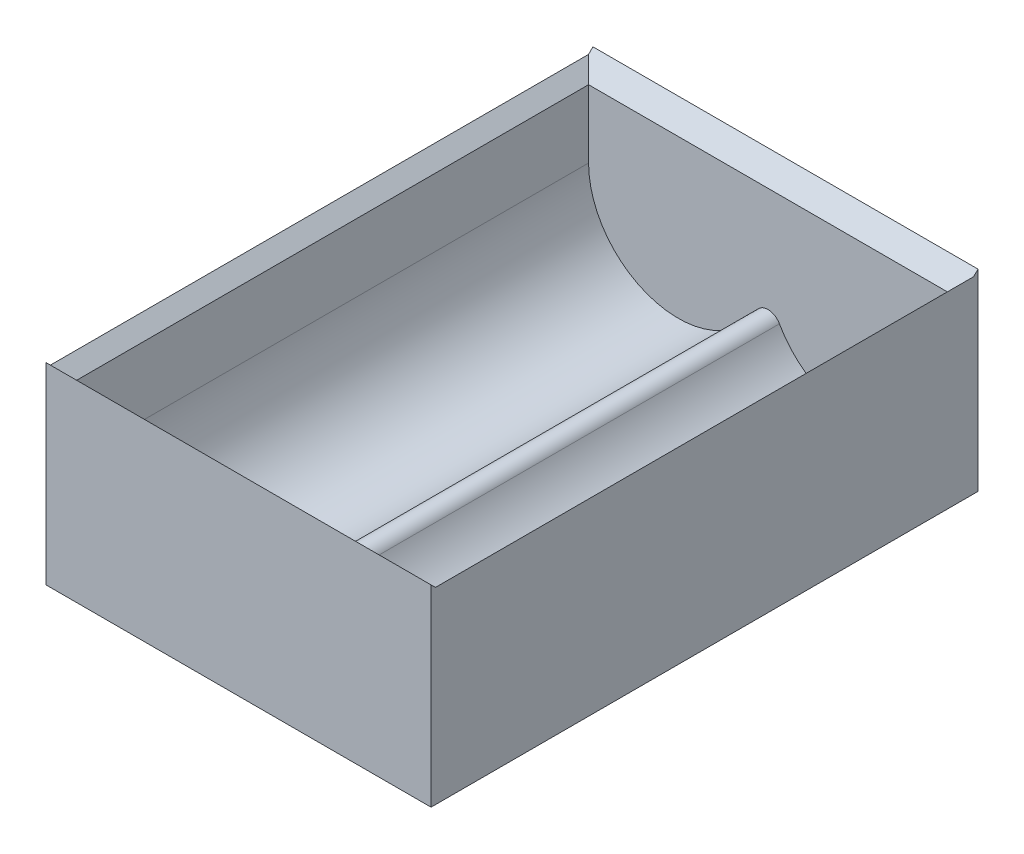
SolidWorks part; units mm, degrees
ref_plane "Front Plane" through (0, 0, 0) normal (0, 0, 1) x (1, 0, 0)
ref_plane "Top Plane" through (0, 0, 0) normal (0, 1, 0) x (1, 0, 0)
ref_plane "Right Plane" through (0, 0, 0) normal (1, 0, 0) x (0, 0, -1)
sketch "Sketch1" plane through (0, 0, 0) normal (0, 1, 0) x (1, 0, 0)
  line L1 (-44, 62.5) -> (44, 62.5)
  line L2 (-44, 62.5) -> (-44, -62.5)
  line L3 (-44, -62.5) -> (44, -62.5)
  line L4 (44, 62.5) -> (44, -62.5)
  line L5 (-44, 62.5) -> (44, -62.5) construction
  line L6 (-44, -62.5) -> (44, 62.5) construction
  point P0 (0, 0)
  dimension "D1" = 125
  dimension "D2" = 88
extrude "Boss-Extrude1" add sketch "Sketch1" along normal blind 50
ref_plane "Plane1" through (0, 0, 58.5) normal (0, 0, 1) x (1, 0, 0)
sketch "Sketch2" plane through (0, 0, 58.5) normal (0, 0, 1) x (1, 0, 0)
  line L1 (0, 0) -> (0, 33.8796) construction
  line L5 (-44, 0) -> (44, 0) construction
  line L6 (-44, 50) -> (-44, 0) construction
  line L7 (-41, 24.5) -> (-41, 66.5)
  line L8 (-41, 66.5) -> (41, 66.5)
  line L9 (41, 24.5) -> (41, 66.5)
  arc A2 (-41, 24.5) -> (0, 24.5) centre (-20.5, 24.5) ccw
  arc A3 (41, 24.5) -> (0, 24.5) centre (20.5, 24.5) cw
  point P1 (0, 0)
  point P13 (0, 66.5)
  dimension "D1" = 24.5
  dimension "D2" = 20.5
  dimension "D3" = 3
  dimension "D4" = 42
extrude "Cut-Extrude1" cut sketch "Sketch2" against normal offset from surface (117 mm away) 4 contours A3 L9 L8 L7 A2 region at (0, 37.2695, 58.5) up to face at (0, 25, -62.5)
fillet "Fillet1" radius 3 1 edges at (0, 24.5, 0)
chamfer "Chamfer1" distance 10 angle 45 4 edges at (0, 50, 58.5) (41, 50, 0) (-41, 50, 0) (0, 50, -58.5)
